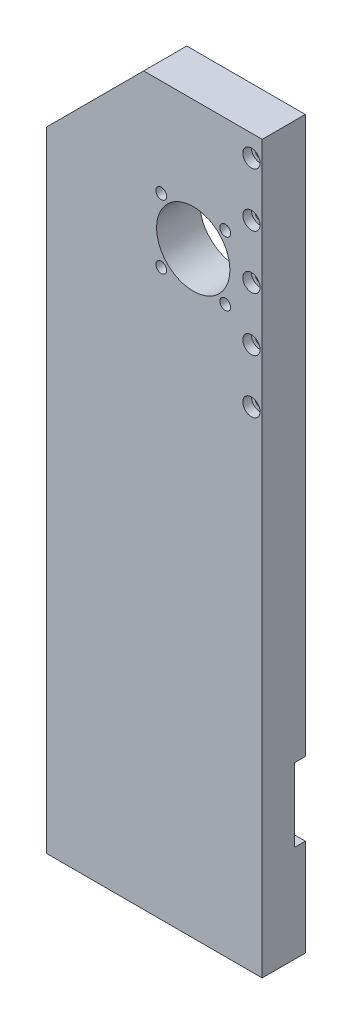
SolidWorks part; units mm, degrees
ref_plane "Front Plane" through (0, 0, 0) normal (0, 0, 1) x (1, 0, 0)
ref_plane "Top Plane" through (0, 0, 0) normal (0, 1, 0) x (1, 0, 0)
ref_plane "Right Plane" through (0, 0, 0) normal (1, 0, 0) x (0, 0, -1)
sketch "Sketch1" plane through (0, 0, 0) normal (0, 0, 1) x (1, 0, 0)
  line L0 (65.7045, 560.5004) -> (50.8553, 575.3496) construction
  line L1 (65.7045, 560.5004) -> (44.7045, 560.5004) construction
  line L2 (65.7045, 560.5004) -> (65.7045, 581.5004) construction
  line L3 (47.7045, 545.8558) -> (47.7045, 439.2537) construction
  line L4 (7.7288, 345.5004) -> (63.5732, 345.5004) construction
  line L5 (97.7045, 283.5004) -> (-2.2955, 283.5004)
  line L6 (97.7045, 283.5004) -> (97.7045, 620.5004)
  line L7 (97.7045, 620.5004) -> (-2.2955, 620.5004)
  line L8 (-2.2955, 283.5004) -> (-2.2955, 620.5004)
  line L9 (97.7045, 283.5004) -> (-2.2955, 620.5004) construction
  line L10 (97.7045, 620.5004) -> (-2.2955, 283.5004) construction
  circle A0 centre (65.7045, 560.5004) radius 17
  circle A1 centre (65.7045, 560.5004) radius 21 construction
  circle A2 centre (80.5538, 575.3496) radius 2.5
  circle A3 centre (80.5538, 545.6511) radius 2.5
  circle A4 centre (50.8553, 545.6511) radius 2.5
  circle A5 centre (50.8553, 575.3496) radius 2.5
  point P5 (50.8553, 575.3496)
  point P6 (80.5538, 575.3496)
  point P7 (80.5538, 545.6511)
  point P8 (50.8553, 545.6511)
  point P19 (47.7045, 452.0004)
  point P35 (34.7045, 358.5004)
  point P36 (60.7045, 358.5004)
  point P37 (60.7045, 332.5004)
  point P38 (34.7045, 332.5004)
  dimension "D2" = 5
  dimension "D3" = 34
  dimension "D4" = 42
  dimension "D1" = 45
  dimension "D5" = 337
  dimension "D6" = 100
  dimension "D7" = 60
  dimension "D8" = 75
  dimension "D9" = 13
  dimension "D11" = 62
  dimension "D12" = 32
extrude "Boss-Extrude1" add sketch "Sketch1" along normal blind 20
chamfer "Chamfer1" distance 45 angle 45 1 edges at (-2.2955, 620.5004, 10)
sketch "Sketch2" plane through (0, 0, 0) normal (0, 0, 1) x (1, 0, 0)
  line L0 (60.7045, 358.5004) -> (34.7045, 332.5004) construction
  line L1 (34.7045, 358.5004) -> (60.7045, 332.5004) construction
  line L3 (97.7045, 328.5004) -> (-2.2955, 328.5004)
  line L4 (97.7045, 328.5004) -> (97.7045, 362.5004)
  line L5 (97.7045, 362.5004) -> (-2.2955, 362.5004)
  line L6 (-2.2955, 328.5004) -> (-2.2955, 362.5004)
  line L7 (97.7045, 328.5004) -> (-2.2955, 362.5004) construction
  line L8 (97.7045, 362.5004) -> (-2.2955, 328.5004) construction
  point P8 (47.7045, 345.5004)
  point P9 (47.7045, 345.5004)
  dimension "D1" = 100
  dimension "D2" = 34
extrude "Cut-Extrude1" cut sketch "Sketch2" along normal blind 5
sketch "Sketch3" plane through (0, 0, 20) normal (0, 0, 1) x (1, 0, 0)
  line L0 (92.7045, 620.5004) -> (92.7045, 500.5004) construction
  line L1 (97.7045, 620.5004) -> (87.7045, 620.5004) construction
  line L2 (97.7045, 620.5004) -> (97.7045, 500.5004) construction
  line L3 (97.7045, 500.5004) -> (87.7045, 500.5004) construction
  line L4 (87.7045, 620.5004) -> (87.7045, 500.5004) construction
  line L5 (97.7045, 560.5004) -> (87.7045, 560.5004) construction
  point P9 (92.7045, 535.5004)
  point P10 (92.7045, 585.5004)
  point P11 (92.7045, 560.5004)
  point P12 (92.7045, 610.5004)
  point P13 (92.7045, 510.5004)
  dimension "D1" = 10
  dimension "D2" = 120
  dimension "D3" = 3
hole_wizard "CBORE for M4 SHCS1" positions "Sketch5" profile "Sketch6" counterbore size "M4" standard "ANSI Metric" end condition through all
sketch "Sketch5" plane through (0, 0, 20) normal (0, 0, 1) x (1, 0, 0)
  point P0 (92.7045, 610.5004)
  point P5 (92.7045, 585.5004)
  point P8 (92.7045, 560.5004)
  point P11 (92.7045, 535.5004)
  point P14 (92.7045, 510.5004)
sketch "Sketch6" plane through (92.7045, 610.5004, 20) normal (1, 0, 0) x (0, -1, 0)
  line L0 (0, 0) -> (0, 20)
  line L1 (0, 20) -> (2.25, 20)
  line L3 (2.25, 20) -> (2.25, 4)
  line L4 (2.25, 4) -> (4, 4)
  line L5 (4, 4) -> (4, 0)
  line L7 (4, 0) -> (0, 0)
  line L11 (0, -6.35) -> (0, 107.95) construction
  dimension "Thru Hole Dia." = 4.5
  dimension "Thru Hole Depth" = 20
  dimension "C'Bore Dia." = 8
  dimension "C'Bore Depth" = 4
